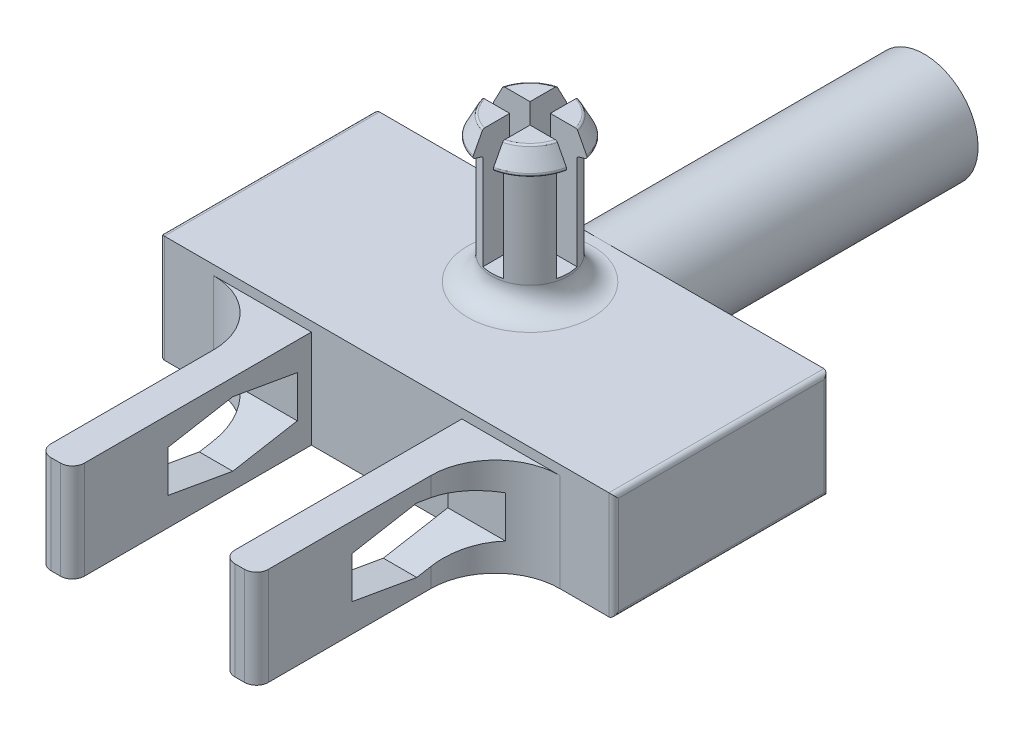
SolidWorks part; units mm, degrees
ref_plane "Front Plane" through (0, 0, 0) normal (0, 0, 1) x (1, 0, 0)
ref_plane "Top Plane" through (0, 0, 0) normal (0, 1, 0) x (1, 0, 0)
ref_plane "Right Plane" through (0, 0, 0) normal (1, 0, 0) x (0, 0, -1)
sketch "Szkic1" plane through (0, 0, 0) normal (0, 1, 0) x (1, 0, 0)
  line L0 (0, -13.1707) -> (0, 4.5) construction
  line L1 (4.55, -4.5) -> (-4.55, -4.5)
  line L2 (9.5, -4.5) -> (9.5, 4.5)
  line L3 (9.5, 4.5) -> (-9.5, 4.5)
  line L4 (-9.5, -4.5) -> (-9.5, 4.5)
  line L5 (9.5, -4.5) -> (-9.5, 4.5) construction
  line L6 (9.5, 4.5) -> (-9.5, -4.5) construction
  line L7 (-9.5, -4.5) -> (-4.55, -4.5)
  line L10 (2.5793, 4.5) -> (-2.5793, 4.5)
  line L13 (-4.55, -4.5) -> (-7.25, -4.5)
  line L14 (-4.55, -4.5) -> (-3.15, -4.5)
  line L15 (-4.55, -4.5) -> (-4.55, -14.5)
  line L16 (-4.55, -14.5) -> (-3.15, -14.5)
  line L17 (-3.15, -4.5) -> (-3.15, -14.5)
  line L18 (4.55, -4.5) -> (3.15, -4.5)
  line L19 (4.55, -4.5) -> (4.55, -14.5)
  line L20 (4.55, -14.5) -> (3.15, -14.5)
  line L21 (3.15, -4.5) -> (3.15, -14.5)
  line L22 (4.55, -4.5) -> (9.5, -4.5)
  line L23 (-4.55, -4.5) -> (-4.55, -7.2)
  line L26 (4.55, -4.5) -> (7.25, -4.5)
  line L27 (4.55, -4.5) -> (4.55, -7.2)
  arc A0 (-4.55, -7.2) -> (-7.25, -4.5) centre (-7.25, -7.2) ccw
  arc A1 (7.25, -4.5) -> (4.55, -7.2) centre (7.25, -7.2) ccw
  point P0 (0, 0)
  dimension "D1" = 9
  dimension "D2" = 19
  dimension "D3" = 10
  dimension "D4" = 1.4
  dimension "D5" = 6.3
  dimension "D6" = 2.7
extrude "Dodanie-wyciągnięcie1" add sketch "Szkic1" along normal blind 4.5 contours L1 L22 L2 L3 L4 L7 region at (0, 0, 0)
extrude "Dodanie-wyciągnięcie2" add sketch "Szkic1<7>" along normal blind 4.1 contours A0 L15 L7 | L17 L1 L15 L16 | A1 L22 L19 | L1 L21 L20 L19 region at (3.85, 0, 9.5) region at (5.1531, 0, 5.1031) region at (-3.85, 0, 9.5) region at (-5.1531, 0, 5.1031)
sketch "Szkic1<7>" plane through (0, 0, 0) normal (0, 1, 0) x (1, 0, 0) same geometry as "Szkic1"
ref_plane "Płaszczyzna1" through (0, 0, -4.5) normal (0, 0, -1) x (-1, 0, 0)
sketch "Szkic2" plane through (0, 0, -4.5) normal (0, 0, -1) x (-1, 0, 0)
  line L0 (0, 0) -> (0, 4.5) construction
  line L1 (-9.5, 4.5) -> (9.5, 4.5) construction
  circle A0 centre (0, 2.25) radius 2.25
  point P5 (0, 2.25)
  dimension "D1" = 4.5
extrude "Dodanie-wyciągnięcie3" add sketch "Szkic2" along normal blind 13.5
ref_plane "Płaszczyzna2" through (-3.15, 0, 0) normal (1, 0, 0) x (0, 0, -1)
sketch "Szkic3" plane through (-3.15, 0, 0) normal (1, 0, 0) x (0, 0, -1)
  line L0 (-7.79, 3.4) -> (-10.49, 2.9239)
  line L1 (-10.49, 2.9239) -> (-10.49, 1.1761)
  line L2 (-10.49, 1.1761) -> (-7.79, 0.7)
  line L3 (-7.79, 0.7) -> (-5.09, 1.1761)
  line L4 (-5.09, 1.1761) -> (-5.09, 2.9239)
  line L5 (-5.09, 2.9239) -> (-7.79, 3.4)
  line L7 (-4.5, 4.1) -> (-14.5, 4.1) construction
  line L8 (-4.5, 0) -> (-14.5, 0) construction
  dimension "D1" = 0.7
  dimension "D2" = 0.7
  dimension "D3" = 100
  dimension "D4" = 100
  dimension "D5" = 5.4
extrude "Wytnij-wyciągnięcie2" cut sketch "Szkic3" along normal through all both and the other way through all
fillet "Zaokrąglenie1" radius 0.5 4 edges at (3.15, 2.05, 14.5) (4.55, 2.05, 14.5) (-4.55, 2.05, 14.5) (-3.15, 2.05, 14.5)
fillet "Zaokrąglenie2" radius 0.2 8 edges at (-9.5, 2.25, -4.5) (-9.5, 4.5, 0) (9.5, 0, 0) (-9.5, 2.25, 4.5) (9.5, 2.25, 4.5) (9.5, 2.25, -4.5) (9.5, 4.5, 0) (-9.5, 0, 0)
ref_plane "Płaszczyzna3" through (0, 4.5, 0) normal (0, 1, 0) x (1, 0, 0)
sketch "Szkic4" plane through (0, 4.5, 0) normal (0, 1, 0) x (1, 0, 0)
  line L0 (-9.3, 1.5) -> (9.3, 1.5) construction
  line L1 (2.475, 4.5) -> (-2.475, 4.5) construction
  line L3 (-9.3, 4.5) -> (-9.3, -4.5) construction
  line L4 (9.3, -4.5) -> (9.3, 4.5) construction
  circle A0 centre (0, 1.5) radius 1.6
  point P6 (0, 1.5)
  dimension "D1" = 3.2
  dimension "D2" = 3
extrude "Dodanie-wyciągnięcie4" add sketch "Szkic4" along normal blind 5.1
ref_plane "Płaszczyzna4" through (0, 9.6, 0) normal (0, 1, 0) x (1, 0, 0)
sketch "Szkic5" plane through (0, 9.6, 0) normal (0, 1, 0) x (1, 0, 0)
  line L0 (0, 3.1) -> (0, -0.1) construction
  circle A0 centre (0, 1.5) radius 1.6 construction
  circle A1 centre (0, 1.5) radius 1.6
  point P5 (0, 1.5)
  dimension "D1" = 3.2
extrude "Dodanie-wyciągnięcie5" add sketch "Szkic5" along normal blind 1
fillet "Zaokrąglenie4" radius 1 1 edges at (0, 4.5, 0.1)
ref_axis "Oś1" through (0, 10.6, -1.5) along (0, -1, 0)
ref_point "Punkt1"
ref_point "Punkt2"
ref_plane "Płaszczyzna5" through (0, 0, 0) normal (1, 0, 0) x (0, 0, -1)
ref_plane "Płaszczyzna Dolnia" through (0, 0, 0) normal (0, -1, 0) x (-1, 0, 0)
ref_plane "Płaszczyzna6" through (0, 10.5, 0) normal (0, 1, 0) x (1, 0, 0)
sketch "Szkic7" plane through (0, 0, 0) normal (1, 0, 0) x (0, 0, -1)
  line L6 (3.1, 10.6) -> (3.1, 9.6)
  line L9 (3.1, 9.6) -> (3.55, 9.7206)
  line L10 (3.55, 9.7206) -> (3.1, 10.6)
  line L13 (1.5, 10.6) -> (1.5, 5.5) construction
  line L16 (4.95, 4.5) -> (-4.95, 4.5) construction
  dimension "D1" = 2.05
  dimension "D2" = 75
  dimension "D4" = 5.1
revolve "Obrót1" add sketch "Szkic7" angle 360 about axis through (0, 10.6, -1.5) along (0, -1, 0)
fillet "Zaokrąglenie5" radius 0.1 3 edges at (0, 9.6, 0.1) (0, 9.7206, 0.55) (0, 10.6, 0.1)
ref_plane "Płaszczyzna7" through (0, 10.6, 0) normal (0, 1, 0) x (1, 0, 0)
sketch "Szkic6" plane through (0, 10.6, 0) normal (0, 1, 0) x (1, 0, 0)
  line L0 (0.425, 4.7145) -> (0.425, 1.925)
  line L1 (-0.425, 4.7145) -> (-0.425, 1.925)
  line L2 (3.2145, 1.925) -> (0.425, 1.925)
  line L3 (3.2145, 1.075) -> (0.425, 1.075)
  line L4 (-0.425, 1.075) -> (-3.2145, 1.075)
  line L5 (-0.425, 1.925) -> (-3.2145, 1.925)
  line L6 (0.425, 1.075) -> (0.425, -1.7145)
  line L7 (-0.425, 1.075) -> (-0.425, -1.7145)
  line L8 (-0.425, 1.925) -> (0.425, 1.075) construction
  arc A4 (0.425, 4.7145) -> (-0.425, 4.7145) centre (0, 1.5) ccw
  arc A5 (3.2145, 1.075) -> (3.2145, 1.925) centre (0, 1.5) ccw
  arc A6 (-0.425, -1.7145) -> (0.425, -1.7145) centre (0, 1.5) ccw
  arc A7 (-3.2145, 1.925) -> (-3.2145, 1.075) centre (0, 1.5) ccw
  point P18 (0, 1.5)
  dimension "D1" = 0.85
  dimension "D2" = 0.85
extrude "Wytnij-wyciągnięcie3" cut sketch "Szkic6" against normal blind 5
